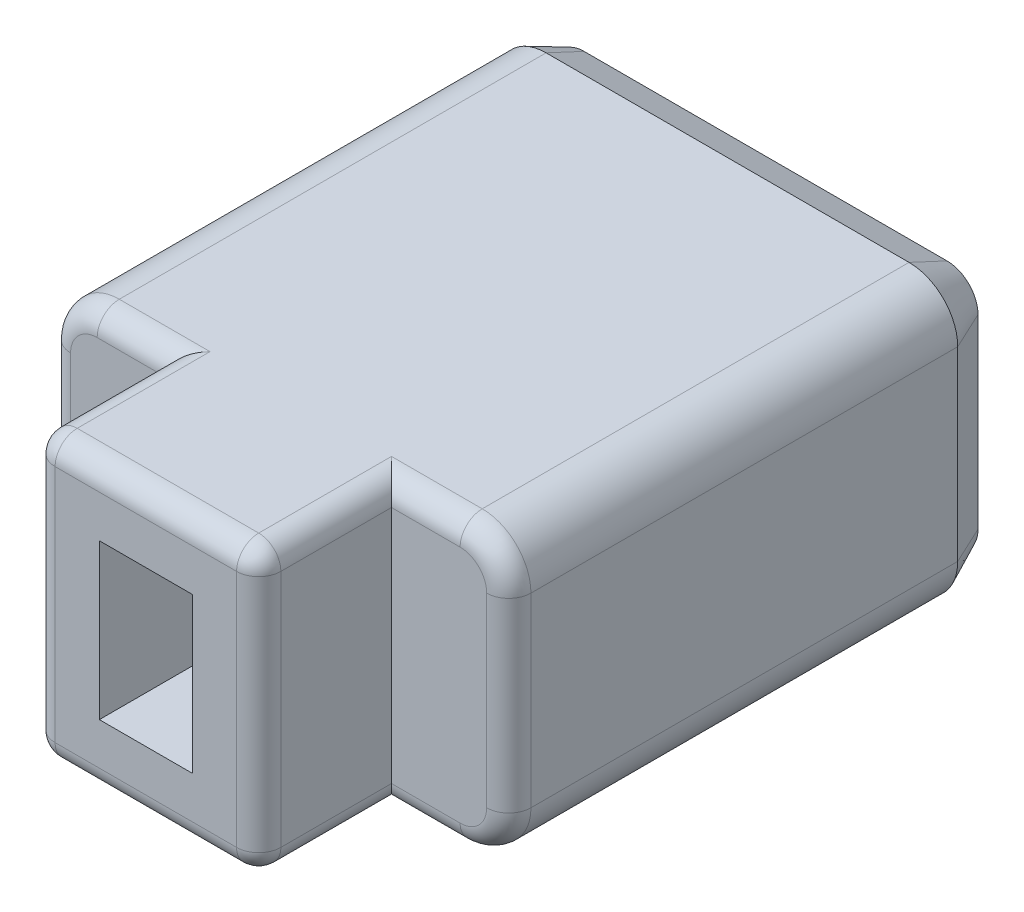
SolidWorks part; units mm, degrees
ref_plane "Plan de face" through (0, 0, 0) normal (0, 0, 1) x (1, 0, 0)
ref_plane "Plan de dessus" through (0, 0, 0) normal (0, 1, 0) x (1, 0, 0)
ref_plane "Plan de droite" through (0, 0, 0) normal (1, 0, 0) x (0, 0, -1)
sketch "Esquisse2" plane through (0, 0, 0) normal (0, 0, 1) x (1, 0, 0)
  line L1 (1.1, 0) -> (9.3, 0)
  line L2 (0, 1.1) -> (0, 5.3)
  line L3 (1.1, 6.4) -> (9.3, 6.4)
  line L4 (10.4, 1.1) -> (10.4, 5.3)
  arc A0 (9.3, 6.4) -> (10.4, 5.3) centre (9.3, 5.3) cw
  arc A1 (9.3, 0) -> (10.4, 1.1) centre (9.3, 1.1) ccw
  arc A2 (1.1, 0) -> (0, 1.1) centre (1.1, 1.1) cw
  arc A3 (0, 5.3) -> (1.1, 6.4) centre (1.1, 5.3) cw
  point P7 (10.4, 6.4)
  point P12 (0, 0)
  point P15 (0, 6.4)
  dimension "D3" = 1.1
  dimension "D1" = 10.4
  dimension "D2" = 6.4
extrude "Boss.-Extru.1" add sketch "Esquisse2" along normal blind 14
sketch "Esquisse3" plane through (0, 0, 14) normal (0, 0, 1) x (1, 0, 0)
  line L0 (0, 5.3) -> (0, 1.1) construction
  line L1 (4.15, 4.95) -> (6.25, 4.95)
  line L2 (4.15, 4.95) -> (4.15, 1.45)
  line L3 (4.15, 1.45) -> (6.25, 1.45)
  line L4 (6.25, 4.95) -> (6.25, 1.45)
  line L5 (10.4, 1.1) -> (10.4, 5.3) construction
  line L6 (9.3, 6.4) -> (1.1, 6.4) construction
  line L7 (1.1, 0) -> (9.3, 0) construction
  dimension "D1" = 2.1
  dimension "D2" = 3.5
  dimension "D3" = 4.15
  dimension "D4" = 4.15
  dimension "D5" = 1.45
  dimension "D6" = 1.45
extrude "Enlèv. mat.-Extru.1" cut sketch "Esquisse3" against normal blind 3
sketch "Esquisse4" plane through (0, 0, 14) normal (0, 0, 1) x (1, 0, 0)
  line L0 (2.65, 6.4) -> (2.65, 0)
  line L1 (9.3, 6.4) -> (1.1, 6.4) construction
  line L2 (1.1, 0) -> (9.3, 0) construction
  line L3 (2.65, 0) -> (7.75, 0)
  line L4 (7.75, 0) -> (7.75, 6.4)
  line L5 (7.75, 6.4) -> (2.65, 6.4)
  line L6 (4.15, 4.95) -> (4.15, 1.45) construction
  line L7 (6.25, 1.45) -> (6.25, 4.95) construction
  dimension "D1" = 1.5
  dimension "D2" = 1.5
extrude "Enlèv. mat.-Extru.2" cut sketch "Esquisse4" against normal blind 3 flip side to cut
fillet "Congé1" radius 0.5 18 edges at (8.525, 0, 11) (10.0778, 0.3222, 11) (10.4, 3.2, 11) (10.0778, 6.0778, 11) (1.875, 6.4, 11) (0.3222, 6.0778, 11) (1.875, 0, 11) (0.3222, 0.3222, 11) (7.75, 6.4, 12.5) (2.65, 6.4, 12.5) (7.75, 0, 12.5) (2.65, 0, 12.5) (2.65, 3.2, 14) (5.2, 6.4, 14) (7.75, 3.2, 14) (5.2, 0, 14) (8.525, 6.4, 11) (0, 3.2, 11)
chamfer "Chanfrein1" distance 0.4 angle 65 8 edges at (5.2, 0, 0) (10.0778, 0.3222, 0) (0.3222, 0.3222, 0) (10.4, 3.2, 0) (0, 3.2, 0) (10.0778, 6.0778, 0) (0.3222, 6.0778, 0) (5.2, 6.4, 0) first distance on face at (5.2, 3.2, 0)
sketch "Esquisse5" plane through (0, 0, 0) normal (0, 0, -1) x (-1, 0, 0)
  line L0 (-0.4, 5.3) -> (-10, 5.3) construction
  arc A0 (-9.3, 6) -> (-10, 5.3) centre (-9.3, 5.3) ccw construction
  text T0 "6" font "Century Gothic" height 4
extrude "Enlèv. mat.-Extru.3" cut sketch "Esquisse5" against normal blind 0.3
extrude "Boss.-Extru.2" add sketch "Esquisse5<2>" along normal blind 0.3 separate body
sketch "Esquisse5<2>" plane through (0, 0, 0) normal (0, 0, -1) x (-1, 0, 0) same geometry as "Esquisse5"
